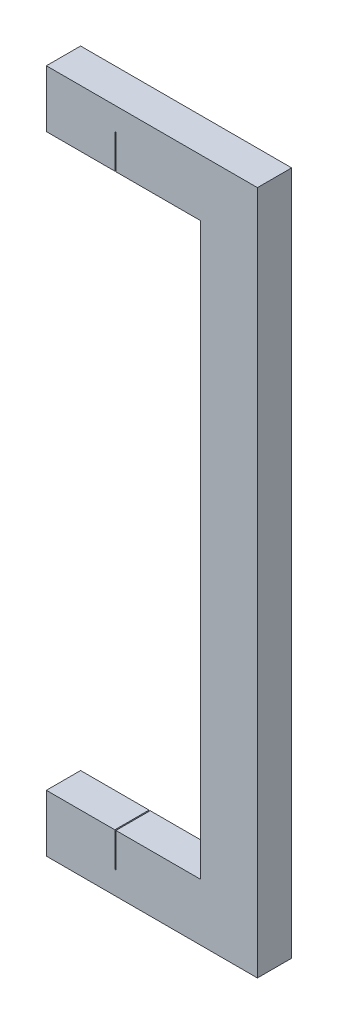
SolidWorks part; units mm, degrees
ref_plane "Front Plane" through (0, 0, 0) normal (0, 0, 1) x (1, 0, 0)
ref_plane "Top Plane" through (0, 0, 0) normal (0, 1, 0) x (1, 0, 0)
ref_plane "Right Plane" through (0, 0, 0) normal (1, 0, 0) x (0, 0, -1)
sketch "Sketch1" plane through (0, 0, 0) normal (0, 0, 1) x (1, 0, 0)
  line L0 (0, 0) -> (18.5, 0)
  line L1 (18.5, 0) -> (18.5, -60)
  line L2 (18.5, -60) -> (0, -60)
  line L3 (0, -60) -> (0, -55)
  line L4 (0, -55) -> (13.5, -55)
  line L5 (13.5, -55) -> (13.5, -5)
  line L6 (13.5, -5) -> (0, -5)
  line L7 (0, -5) -> (0, 0)
  dimension "D1" = 5
  dimension "D2" = 5
  dimension "D3" = 5
  dimension "D4" = 13.5
  dimension "D5" = 60
extrude "Boss-Extrude1" add sketch "Sketch1" along normal blind 3
sketch "Sketch2" plane through (0, -55, 0) normal (0, 1, 0) x (1, 0, 0)
  line L0 (18.5, -1.5) -> (6.05, -1.5) construction
  line L1 (18.5, -3) -> (18.5, 0) construction
  line L2 (13.5, 0) -> (0, 0) construction
  line L3 (6, -3) -> (6.1, -3)
  line L4 (6, -3) -> (6, 0)
  line L5 (6, 0) -> (6.1, 0)
  line L6 (6.1, -3) -> (6.1, 0)
  line L7 (6, -3) -> (6.1, 0) construction
  line L8 (6, 0) -> (6.1, -3) construction
extrude "Cut-Extrude1" cut sketch "Sketch2" against normal blind 3
sketch "Sketch3" plane through (0, -5, 0) normal (0, -1, 0) x (1, 0, 0)
  line L0 (18.5, 1.5) -> (6.05, 1.5) construction
  line L1 (18.5, 3) -> (18.5, 0) construction
  line L2 (0, 3) -> (13.5, 3) construction
  line L3 (6, 0) -> (6.1, 0)
  line L4 (6, 0) -> (6, 3)
  line L5 (6, 3) -> (6.1, 3)
  line L6 (6.1, 0) -> (6.1, 3)
  line L7 (6, 0) -> (6.1, 3) construction
  line L8 (6, 3) -> (6.1, 0) construction
extrude "Cut-Extrude2" cut sketch "Sketch3" against normal blind 3
equation "\"A.L\"= 0.06m"
equation "\"A.h\"= 0.005m"
equation "\"A.d\"= 0.003m"
equation "\"A.delta\"= 45.0001"
equation "\"A.w\"= 0.02m"
equation "\"A.v\"= 0.03m"
equation "\"A.s\"= 0.0075m"
equation "\"A.t\"= 0.005m"
equation "\"B.L\"= 0.04m"
equation "\"B.h\"= 0.004m"
equation "\"B.s\"= 0.008m"
equation "\"B.t\"= 0.004m"
equation "\"C.h\"= 0.0062m"
equation "\"C.d\"= 0.003m"
equation "\"C.L\"= 0.05m"
equation "\"C.wmax\"= 0.005m"
equation "\"D.L\"= 0.045m"
equation "\"D.h\"= 0.004m"
equation "\"D.s\"= 0.01m"
equation "\"D.t\"= 0.004m"
equation "\"a_h\"= 0.0001m"
equation "\"a_d\"= 0.003m"
equation "\"a_L\"= 0.01m"
equation "\"b_h\"= 0.0004m"
equation "\"b_d\"= 0.003m"
equation "\"b_L\"= 0.01m"
equation "\"c_h\"= 0.0001m"
equation "\"c_d\"= 0.003m"
equation "\"c_L\"= 0.01m"
equation "\"d_h\"= 0.0001m"
equation "\"d_d\"= 0.003m"
equation "\"d_L\"= 0.01m"
equation "\"S.h\"= 0.015m"
equation "\"S.L\"= 0.0559m"
equation "\"D1@Sketch1\"=\"A.h\""
equation "\"D2@Sketch1\"=\"A.t\""
equation "\"D3@Sketch1\"=\"A.t\""
equation "\"D4@Sketch1\"=\"A.s\"+0.006"
equation "\"D5@Sketch1\"=\"A.L\""
equation "\"D1@Boss-Extrude1\"=\"A.d\""
equation "\"D1@Sketch2\"=\"A.h\"+\"A.s\"-\"a_h\"/2"
equation "\"D2@Sketch2\"=\"d_h\""
equation "\"D1@Sketch3\"=\"A.h\"+\"A.s\"-\"d_h\"/2"
equation "\"D2@Sketch3\"=\"d_h\""
